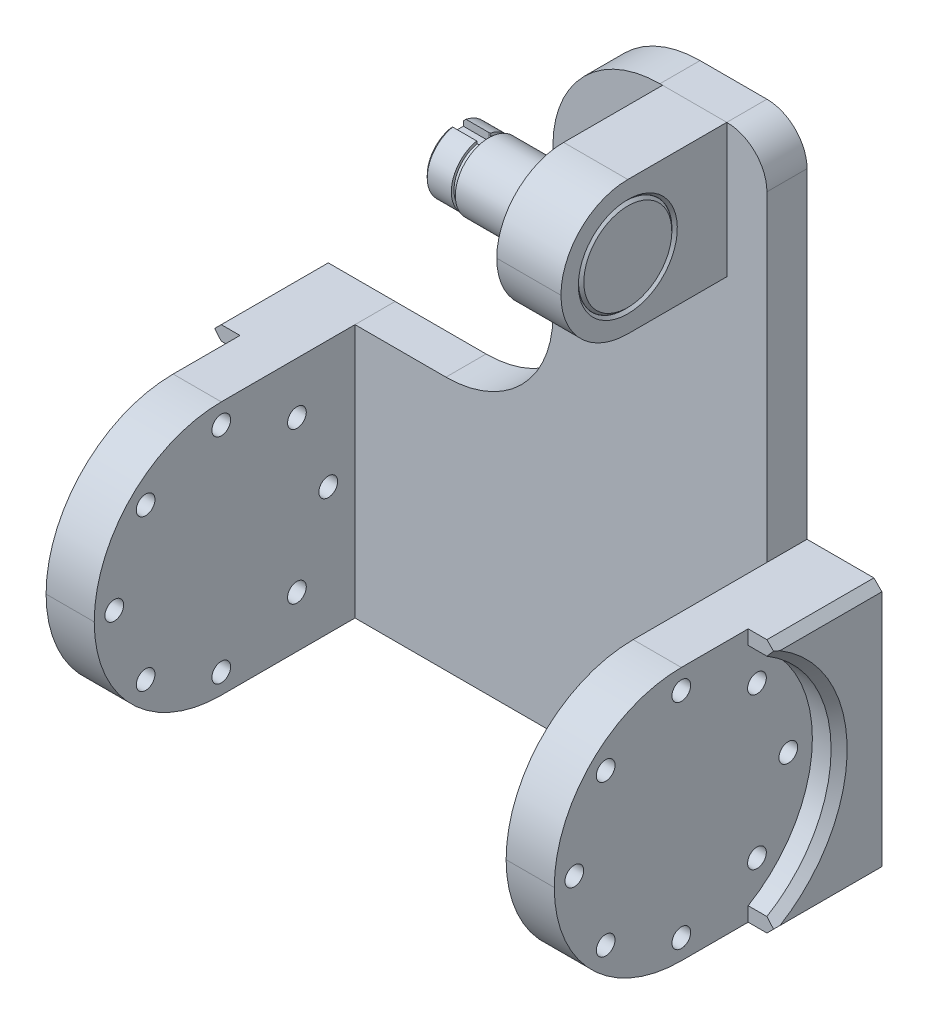
SolidWorks part; units mm, degrees
ref_plane "前视" through (0, 0, 0) normal (0, 0, 1) x (1, 0, 0)
ref_plane "上视" through (0, 0, 0) normal (0, 1, 0) x (1, 0, 0)
ref_plane "右视" through (0, 0, 0) normal (1, 0, 0) x (0, 0, -1)
sketch "草图1" plane through (0, 0, 0) normal (0, 0, 1) x (1, 0, 0)
  line L0 (-80, 0) -> (-80, -135)
  line L1 (0, 0) -> (-80, 0)
  line L2 (0, 0) -> (0, -230)
  line L3 (0, -230) -> (-154, -230)
  line L4 (-154, -135) -> (-154, -230)
  line L5 (-80, -135) -> (-154, -135)
  line L6 (0, -135) -> (-154, -135) construction
  line L7 (-80, 0) -> (-80, -230) construction
  dimension "D1" = 230
  dimension "D2" = 154
  dimension "D3" = 80
  dimension "D4" = 95
extrude "拉伸1" add sketch "草图1" along normal blind 15
fillet "圆角1" radius 40 1 edges at (-80, -135, 7.5)
sketch "草图2" plane through (0, 0, 0) normal (1, 0, 0) x (0, 0, -1)
  line L1 (0, -230) -> (-112.5, -230)
  line L2 (0, -230) -> (0, -135)
  line L3 (0, -135) -> (-112.5, -135)
  line L4 (-112.5, -230) -> (-112.5, -135)
  dimension "D1" = 95
  dimension "D2" = 112.5
extrude "拉伸2" add sketch "草图2" along normal blind 28 separate body
sketch "草图3" plane through (-154, 0, 0) normal (-1, 0, 0) x (0, 0, 1)
  line L1 (0, -135) -> (112.5, -135)
  line L2 (0, -135) -> (0, -230)
  line L3 (0, -230) -> (112.5, -230)
  line L4 (112.5, -135) -> (112.5, -230)
extrude "拉伸3" add sketch "草图3" along normal blind 28 separate body
fillet "圆角2" radius 47.5 2 edges at (14, -230, 112.5) (14, -135, 112.5)
fillet "圆角3" radius 47.5 2 edges at (-168, -135, 112.5) (-168, -230, 112.5)
sketch "草图4" plane through (28, 0, 0) normal (1, 0, 0) x (0, 0, -1)
  circle A0 centre (-65, -182.5) radius 49
  dimension "D1" = 98
extrude "切除-拉伸1" cut sketch "草图4" against normal blind 10
sketch "草图5" plane through (-182, 0, 0) normal (-1, 0, 0) x (0, 0, 1)
  circle A0 centre (65, -182.5) radius 49
  dimension "D1" = 98
extrude "切除-拉伸2" cut sketch "草图5" against normal blind 10
sketch "草图6" plane through (-182, 0, 0) normal (-1, 0, 0) x (0, 0, 1)
  line L0 (0, -230) -> (52.9688, -230) construction
  line L1 (52.9688, -135) -> (40, -135)
  line L2 (52.9688, -135) -> (52.9688, -230)
  line L3 (52.9688, -230) -> (40, -230)
  line L4 (40, -135) -> (40, -230)
  line L5 (0, -135) -> (0, -230) construction
  dimension "D1" = 40
extrude "切除-拉伸3" cut sketch "草图6" against normal blind 10
sketch "草图7" plane through (28, 0, 0) normal (1, 0, 0) x (0, 0, -1)
  line L1 (-40, -135) -> (-52.9688, -135)
  line L2 (-40, -135) -> (-40, -230)
  line L3 (-40, -230) -> (-52.9688, -230)
  line L4 (-52.9688, -135) -> (-52.9688, -230)
extrude "切除-拉伸4" cut sketch "草图7" against normal blind 10
sketch "草图8" plane through (18, 0, 0) normal (1, 0, 0) x (0, 0, -1)
  circle A0 centre (-36.7157, -154.2157) radius 3.5
  circle A1 centre (-25, -182.5) radius 3.5
  circle A2 centre (-36.7157, -210.7843) radius 3.5
  circle A3 centre (-65, -222.5) radius 3.5
  circle A4 centre (-93.2843, -210.7843) radius 3.5
  circle A5 centre (-105, -182.5) radius 3.5
  circle A6 centre (-93.2843, -154.2157) radius 3.5
  circle A7 centre (-65, -142.5) radius 3.5
extrude "切除-拉伸5" cut sketch "草图8" against normal blind 30
sketch "草图9" plane through (-172, 0, 0) normal (-1, 0, 0) x (0, 0, 1)
  circle A0 centre (93.2843, -154.2157) radius 3.5
  circle A1 centre (105, -182.5) radius 3.5
  circle A2 centre (65, -142.5) radius 3.5
  circle A3 centre (93.2843, -210.7843) radius 3.5
  circle A4 centre (65, -222.5) radius 3.5
  circle A5 centre (36.7157, -210.7843) radius 3.5
  circle A6 centre (25, -182.5) radius 3.5
  circle A7 centre (36.7157, -154.2157) radius 3.5
extrude "切除-拉伸6" cut sketch "草图9" against normal blind 30
sketch "草图10" plane through (0, 0, 0) normal (0, 0, -1) x (-1, 0, 0)
  circle A0 centre (-18, -145) radius 4
  circle A1 centre (172, -145) radius 4
  circle A2 centre (-18, -170) radius 4
  circle A3 centre (172, -170) radius 4
  circle A4 centre (-18, -195) radius 4
  circle A5 centre (172, -195) radius 4
  circle A6 centre (-18, -220) radius 4
  circle A7 centre (172, -220) radius 4
extrude "切除-拉伸7" cut sketch "草图10" against normal blind 15
fillet "圆角4" radius 40 1 edges at (-80, 0, 7.5)
fillet "圆角5" radius 15 1 edges at (0, 0, 7.5)
sketch "草图11" plane through (0, 0, 15) normal (0, 0, 1) x (1, 0, 0)
  line L1 (-15, 0) -> (-39, 0)
  line L2 (-15, 0) -> (-15, -50)
  line L3 (-15, -50) -> (-39, -50)
  line L4 (-39, 0) -> (-39, -50)
  dimension "D1" = 50
  dimension "D2" = 24
extrude "拉伸4" add sketch "草图11" along normal blind 62 separate body
fillet "圆角6" radius 25 2 edges at (-27, -50, 77) (-27, 0, 77)
sketch "草图12" plane through (-15, 0, 0) normal (1, 0, 0) x (0, 0, -1)
  circle A0 centre (-52, -25) radius 17.5
extrude "切除-拉伸8" cut sketch "草图12" against normal blind 3
sketch "草图13" plane through (-18, 0, 0) normal (1, 0, 0) x (0, 0, -1)
  circle A0 centre (-52, -25) radius 15
extrude "切除-拉伸9" cut sketch "草图13" against normal blind 73
ref_plane "基准面1" through (-17.999, 0, 0) normal (1, 0, 0) x (0, 0, -1)
sketch "草图14" plane through (-17.999, 0, 0) normal (1, 0, 0) x (0, 0, -1)
  circle A0 centre (-52, -25) radius 17.45
extrude "拉伸5" add sketch "草图14" along normal blind 3
chamfer "倒角1" distance 1 angle 45 1 edges at (-14.999, -7.55, 52)
chamfer "倒角2" distance 1 angle 45 1 edges at (-15, -7.5, 52)
sketch "草图15" plane through (-17.999, 0, 0) normal (-1, 0, 0) x (0, 0, 1)
  circle A0 centre (52, -25) radius 14.95
extrude "拉伸6" add sketch "草图15" along normal blind 27
sketch "草图16" plane through (-44.999, 0, 0) normal (-1, 0, 0) x (0, 0, 1)
  circle A0 centre (52, -25) radius 12.5
extrude "拉伸7" add sketch "草图16" along normal blind 22
sketch "草图17" plane through (-66.999, 0, 0) normal (-1, 0, 0) x (0, 0, 1)
  circle A0 centre (52, -25) radius 12
extrude "拉伸8" add sketch "草图17" along normal blind 12
chamfer "倒角3" distance 1 angle 45 1 edges at (-78.999, -37, 52)
ref_plane "基准面2" through (0, -25, 0) normal (0, 1, 0) x (-1, 0, 0)
sketch "草图18" plane through (0, -25, 0) normal (0, 1, 0) x (-1, 0, 0)
  line L1 (66.999, 64) -> (68.999, 64)
  line L2 (66.999, 64) -> (66.999, 63)
  line L3 (66.999, 63) -> (68.999, 63)
  line L4 (68.999, 64) -> (68.999, 63)
  dimension "D1" = 2
  dimension "D2" = 1
ref_axis "基准轴1" through (-44.999, -25, 52) along (-1, 0, 0)
revolve "切除-旋转1" cut sketch "草图18" angle 360 about axis through (-44.999, -25, 52) along (-1, 0, 0)
ref_plane "基准面3" through (0, -13, 0) normal (0, 1, 0) x (-1, 0, 0)
sketch "草图19" plane through (0, -13, 0) normal (0, 1, 0) x (-1, 0, 0)
  line L0 (66.999, 41) -> (66.999, 63) construction
  line L1 (66.999, 54.5) -> (78.999, 54.5)
  line L2 (66.999, 54.5) -> (66.999, 49.5)
  line L3 (66.999, 49.5) -> (78.999, 49.5)
  line L4 (78.999, 54.5) -> (78.999, 49.5)
  line L5 (78.999, 41) -> (78.999, 63) construction
extrude "切除-拉伸10" cut sketch "草图19" against normal blind 3
fillet "圆角7" radius 2.5 2 edges at (-66.999, -15.1439, 49.5) (-66.999, -15.1439, 54.5)
chamfer "倒角4" distance 3 angle 45 1 edges at (-182, -182.5, 16)
chamfer "倒角5" distance 3 angle 45 1 edges at (28, -182.5, 16)
chamfer "倒角6" distance 3 angle 45 2 edges at (-182, -135, 20) (-182, -230, 20)
chamfer "倒角7" distance 3 angle 45 2 edges at (28, -135, 20) (28, -230, 20)
